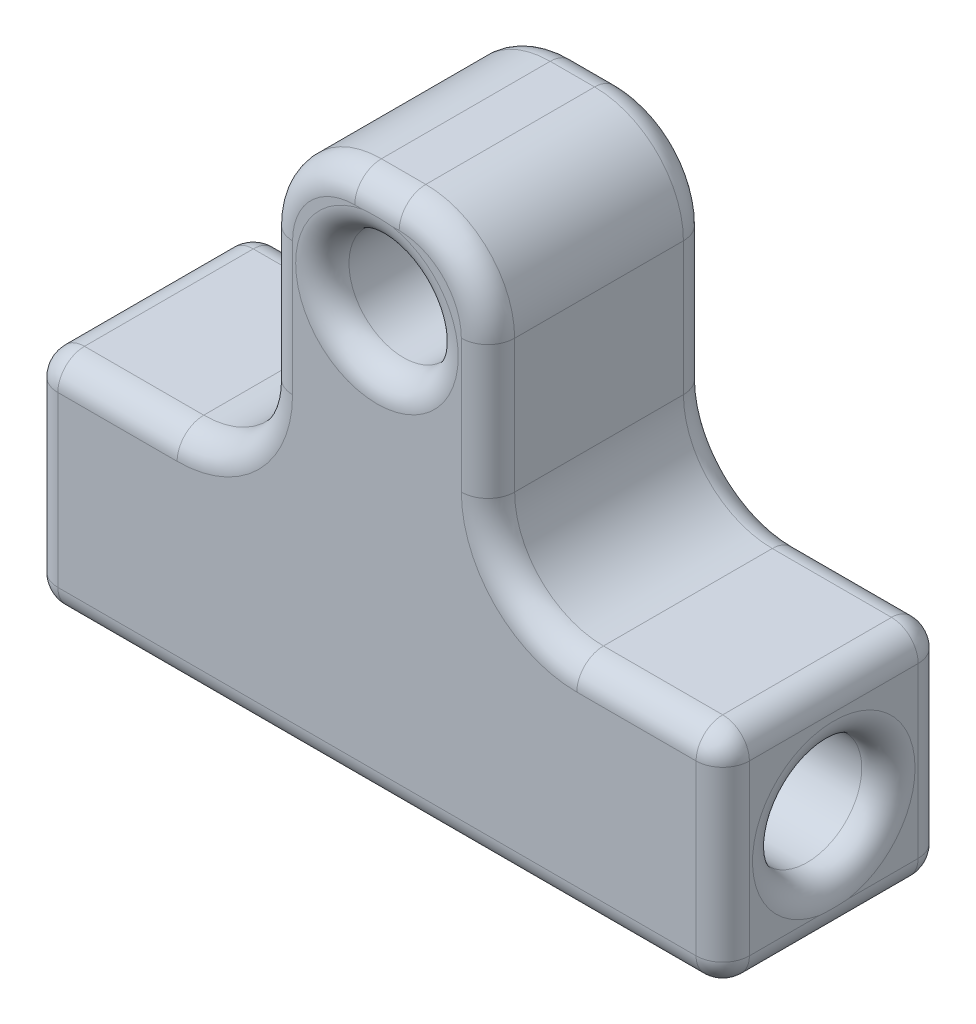
SolidWorks part; units mm, degrees
ref_plane "Front Plane" through (0, 0, 0) normal (0, 0, 1) x (1, 0, 0)
ref_plane "Top Plane" through (0, 0, 0) normal (0, 1, 0) x (1, 0, 0)
ref_plane "Right Plane" through (0, 0, 0) normal (1, 0, 0) x (0, 0, -1)
sketch "Sketch1" plane through (0, 0, 0) normal (0, 0, 1) x (1, 0, 0)
  line L0 (0, 42.6446) -> (0, -51.4876) construction
  line L1 (-40.9091, 0) -> (51.7355, 0) construction
  line L2 (22.5, -5) -> (38.9256, -5)
  line L3 (-2.5, 30) -> (2.5, 30)
  line L4 (-12.5, 20) -> (-12.5, 5)
  line L5 (-12.5, -30) -> (12.5, -30)
  line L6 (12.5, 20) -> (12.5, 5)
  line L7 (-12.5, 30) -> (12.5, -30) construction
  line L8 (-12.5, -30) -> (12.5, 30) construction
  line L9 (-38.9256, -5) -> (-22.5, -5)
  line L10 (-38.9256, -5) -> (-38.9256, -30)
  line L11 (-38.9256, -30) -> (38.9256, -30)
  line L12 (38.9256, -5) -> (38.9256, -30)
  line L13 (-38.9256, -5) -> (38.9256, -30) construction
  line L14 (-38.9256, -30) -> (38.9256, -5) construction
  arc A0 (2.5, 30) -> (12.5, 20) centre (2.5, 20) cw
  arc A1 (-2.5, 30) -> (-12.5, 20) centre (-2.5, 20) ccw
  arc A2 (12.5, 5) -> (22.5, -5) centre (22.5, 5) ccw
  arc A3 (-12.5, 5) -> (-22.5, -5) centre (-22.5, 5) cw
  circle A4 centre (0, 18) radius 6.15
  point P5 (0, 0)
  point P10 (0, -17.5)
  point P25 (12.5, -5)
  dimension "D4" = 10
  dimension "D5" = 12.3
  dimension "D1" = 25
  dimension "D2" = 60
  dimension "D3" = 25
  dimension "D6" = 12
extrude "Boss-Extrude1" add sketch "Sketch1" along normal blind 25 contours A3 L9 L10 L11 L12 L2 A2 L6 A0 L3 A1 L4 | A4
sketch "Sketch2" plane through (38.9256, 0, 0) normal (1, 0, 0) x (0, 0, -1)
  line L0 (-12.5, -5) -> (-12.5, -30) construction
  line L1 (-25, -5) -> (0, -5) construction
  line L2 (-25, -30) -> (0, -30) construction
  circle A0 centre (-12.5, -18) radius 6.15
  dimension "D1" = 12.3
  dimension "D2" = 12
extrude "Cut-Extrude1" cut sketch "Sketch2" against normal through all
fillet "Fillet1" radius 3 32 edges at (-38.9256, -5, 12.5) (-38.9256, -30, 12.5) (-38.9256, -18, 6.35) (6.15, 18, 0) (-15.4289, -2.0711, 0) (-30.7128, -5, 0) (-38.9256, -17.5, 0) (0, -30, 0) (15.4289, -2.0711, 0) (12.5, 12.5, 0) (9.5711, 27.0711, 0) (0, 30, 0) (-9.5711, 27.0711, 0) (-12.5, 12.5, 0) (30.7128, -5, 0) (6.15, 18, 25) (-9.5711, 27.0711, 25) (0, 30, 25) (9.5711, 27.0711, 25) (12.5, 12.5, 25) (15.4289, -2.0711, 25) (30.7128, -5, 25) (0, -30, 25) (-38.9256, -17.5, 25) (-30.7128, -5, 25) (-15.4289, -2.0711, 25) (-12.5, 12.5, 25) (38.9256, -30, 12.5) (38.9256, -17.5, 25) (38.9256, -5, 12.5) (38.9256, -17.5, 0) (38.9256, -18, 6.35)
